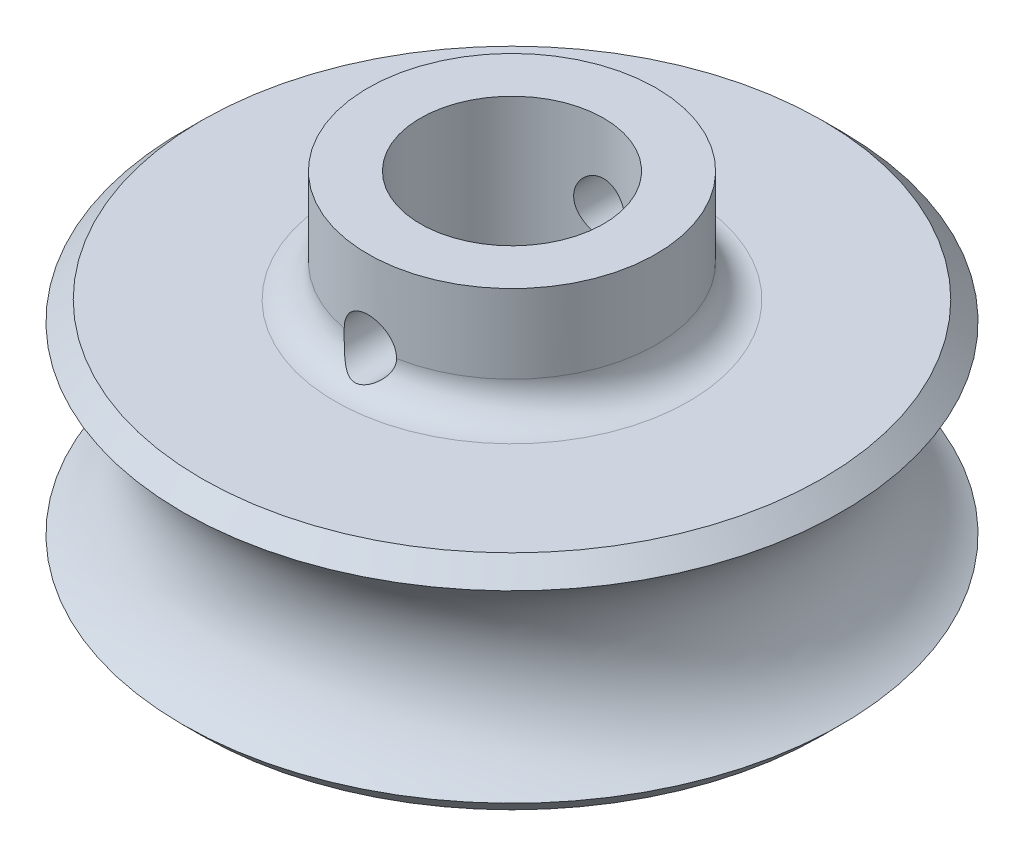
SolidWorks part; units mm, degrees
ref_plane "Plan de face" through (0, 0, 0) normal (0, 0, 1) x (1, 0, 0)
ref_plane "Plan de dessus" through (0, 0, 0) normal (0, 1, 0) x (1, 0, 0)
ref_plane "Plan de droite" through (0, 0, 0) normal (1, 0, 0) x (0, 0, -1)
sketch "Sketch1" plane through (0, 0, 0) normal (0, 0, 1) x (1, 0, 0)
  line L0 (3.5, 8.5) -> (3.5, 0)
  line L2 (0, 0) -> (0, 8.5) construction
  line L4 (3.5, 0) -> (11.85, 0)
  line L5 (6.75, 8.5) -> (11.85, 8.5)
  line L6 (11.85, 0) -> (12.5871, 0.7371)
  line L7 (11.85, 8.5) -> (12.5871, 7.7629)
  line L8 (0, 0) -> (3.5, 0) construction
  line L9 (0, 4.25) -> (14.5, 4.25) construction
  line L10 (5.5, 9.75) -> (5.5, 12.75)
  line L11 (3.5, 8.5) -> (3.5, 12.75)
  line L12 (3.5, 12.75) -> (5.5, 12.75)
  line L13 (6.75, 8.5) -> (3.5, 8.5) construction
  arc A2 (12.5871, 7.7629) -> (12.5871, 0.7371) centre (14.5, 4.25) ccw
  arc A3 (6.75, 8.5) -> (5.5, 9.75) centre (6.75, 9.75) cw
  point P16 (10.5, 4.25)
  dimension "D3" = 8
  dimension "D9" = 4.25
  dimension "D8" = 1.25
  dimension "D1" = 8.5
  dimension "D2" = 8.35
  dimension "D4" = 3.5
  dimension "D5" = 14.5
  dimension "D6" = 1.0424
  dimension "D7" = 1.0424
  dimension "D10" = 6.35
  dimension "D11" = 2
revolve "Revolve1" add sketch "Sketch1" angle 360 about L2
sketch "Sketch2" plane through (0, 0, 0) normal (0, 0, 1) x (1, 0, 0)
  line L1 (0, 9.75) -> (0, 12.75) construction
  line L2 (3.5, 12.75) -> (-3.5, 12.75) construction
  circle A0 centre (0, 9.75) radius 1
  dimension "D2" = 2
  dimension "D1" = 3
extrude "Cut-Extrude1" cut sketch "Sketch2" against normal up to next and the other way up to next
